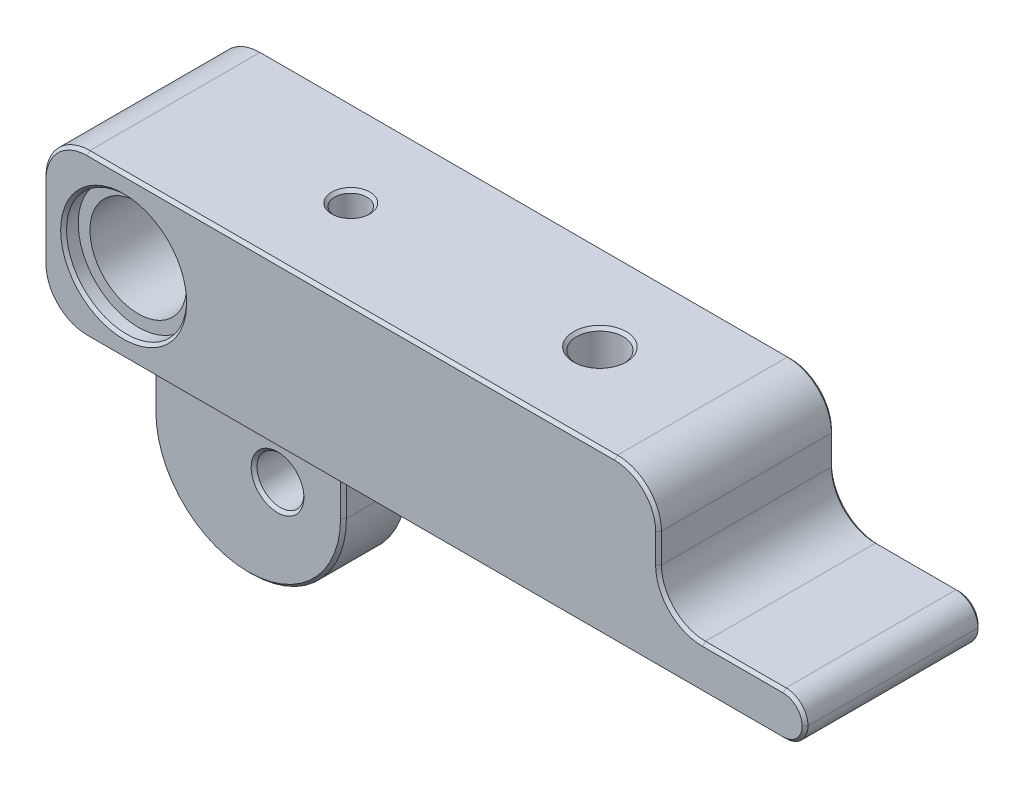
SolidWorks part; units mm, degrees
ref_plane "Спереди" through (0, 0, 0) normal (0, 0, 1) x (1, 0, 0)
ref_plane "Сверху" through (0, 0, 0) normal (0, 1, 0) x (1, 0, 0)
ref_plane "Справа" through (0, 0, 0) normal (1, 0, 0) x (0, 0, -1)
sketch "Эскиз1" plane through (0, 0, 0) normal (0, 0, 1) x (1, 0, 0)
  line L1 (0, 0) -> (52, 0)
  line L2 (0, 0) -> (0, 27)
  line L3 (0, 27) -> (52, 27)
  line L4 (52, 0) -> (52, 27)
  dimension "D1" = 52
  dimension "D2" = 27
extrude "Бобышка-Вытянуть1" add sketch "Эскиз1" along normal blind 12
sketch "Эскиз2" plane through (0, 0, 12) normal (0, 0, 1) x (1, 0, 0)
  line L0 (52, 0) -> (52, 27) construction
  line L1 (0, 0) -> (52, 0)
  line L2 (0, 0) -> (0, 16)
  line L3 (0, 16) -> (52, 16)
  line L4 (52, 0) -> (52, 16)
  line L5 (52, 27) -> (0, 27) construction
  dimension "D1" = 11
extrude "Вырез-Вытянуть1" cut sketch "Эскиз2" against normal blind 7.5
sketch "Эскиз3" plane through (0, 0, 12) normal (0, 0, 1) x (1, 0, 0)
  line L1 (52, 27) -> (42, 27)
  line L2 (52, 27) -> (52, 19)
  line L3 (52, 19) -> (42, 19)
  line L4 (42, 27) -> (42, 19)
  dimension "D1" = 8
  dimension "D2" = 10
extrude "Вырез-Вытянуть2" cut sketch "Эскиз3" against normal blind 12
sketch "Эскиз4" plane through (0, 0, 4.5) normal (0, 0, 1) x (1, 0, 0)
  line L0 (0, 0) -> (52, 0) construction
  line L1 (52, 16) -> (13, 16)
  line L2 (52, 16) -> (52, 0)
  line L3 (52, 0) -> (13, 0)
  line L4 (13, 16) -> (13, 0)
  dimension "D1" = 39
extrude "Вырез-Вытянуть3" cut sketch "Эскиз4" against normal blind 12
fillet "Скругление1" radius 5 1 edges at (13, 16, 2.25)
fillet "Скругление2" radius 6.5 2 edges at (0, 0, 2.25) (13, 0, 2.25)
fillet "Скругление3" radius 1.5 2 edges at (52, 16, 6) (52, 19, 6)
fillet "Скругление4" radius 3 1 edges at (42, 27, 6)
fillet "Скругление5" radius 3 2 edges at (0, 16, 8.25) (0, 27, 6)
sketch "Эскиз5" plane through (0, 0, 12) normal (0, 0, 1) x (1, 0, 0)
  line L0 (0, 24) -> (0, 19) construction
  circle A0 centre (5.5, 21.5) radius 3.3
  dimension "D1" = 5.5
extrude "Вырез-Вытянуть4" cut sketch "Эскиз5" against normal blind 12
sketch "Эскиз6" plane through (0, 0, 12) normal (0, 0, 1) x (1, 0, 0)
  circle A0 centre (5.5, 21.5) radius 4.1
extrude "Вырез-Вытянуть5" cut sketch "Эскиз6" against normal blind 1
sketch "Эскиз7" plane through (0, 0, 4.5) normal (0, 0, 1) x (1, 0, 0)
  line L0 (0, 19) -> (0, 6.5) construction
  line L1 (18, 16) -> (3, 16) construction
  circle A0 centre (8.5, 6.5) radius 1.6
  dimension "D1" = 8.5
  dimension "D2" = 9.5
extrude "Вырез-Вытянуть6" cut sketch "Эскиз7" against normal blind 7
sketch "Эскиз8" plane through (0, 27, 0) normal (0, 1, 0) x (1, 0, 0)
  line L0 (0, -12) -> (0, 0) construction
  circle A0 centre (15, -6) radius 1.1
  dimension "D1" = 15
extrude "Вырез-Вытянуть7" cut sketch "Эскиз8" against normal blind 14.7
sketch "Эскиз9" plane through (0, 27, 0) normal (0, 1, 0) x (1, 0, 0)
  line L0 (0, -12) -> (0, 0) construction
  circle A0 centre (32, -6) radius 1.6
  dimension "D1" = 32
extrude "Вырез-Вытянуть8" cut sketch "Эскиз9" against normal blind 14.7
fillet "Скругление6" radius 3 1 edges at (42, 19, 6)
chamfer "Фаска2" distance 0.2 angle 45 28 edges at (1.9038, 1.9038, 0) (11.0962, 1.9038, 0) (13, 8.75, 0) (14.4645, 14.5355, 0) (34.25, 16, 0) (51.5607, 16.4393, 0) (51.5607, 18.5607, 0) (47.75, 19, 0) (42.8787, 19.8787, 0) (42, 23, 0) (41.1213, 26.1213, 0) (21, 27, 0) (0.8787, 26.1213, 0) (0, 15.25, 0) (8.8, 21.5, 0) (6.9, 6.5, 0) (0.8787, 26.1213, 12) (21, 27, 12) (41.1213, 26.1213, 12) (42, 23, 12) (42.8787, 19.8787, 12) (47.75, 19, 12) (51.5607, 18.5607, 12) (51.5607, 16.4393, 12) (26.75, 16, 12) (0.8787, 16.8787, 12) (0, 21.5, 12) (9.6, 21.5, 12)
chamfer "Фаска3" distance 0.2 angle 45 5 edges at (0, 12.75, 4.5) (1.9038, 1.9038, 4.5) (14.4645, 14.5355, 4.5) (11.0962, 1.9038, 4.5) (13, 8.75, 4.5)
chamfer "Фаска4" distance 0.2 angle 45 5 edges at (10.1, 6.5, 4.5) (32, 16, 7.6) (15, 16, 7.1) (32, 27, 7.6) (15, 27, 7.1)
